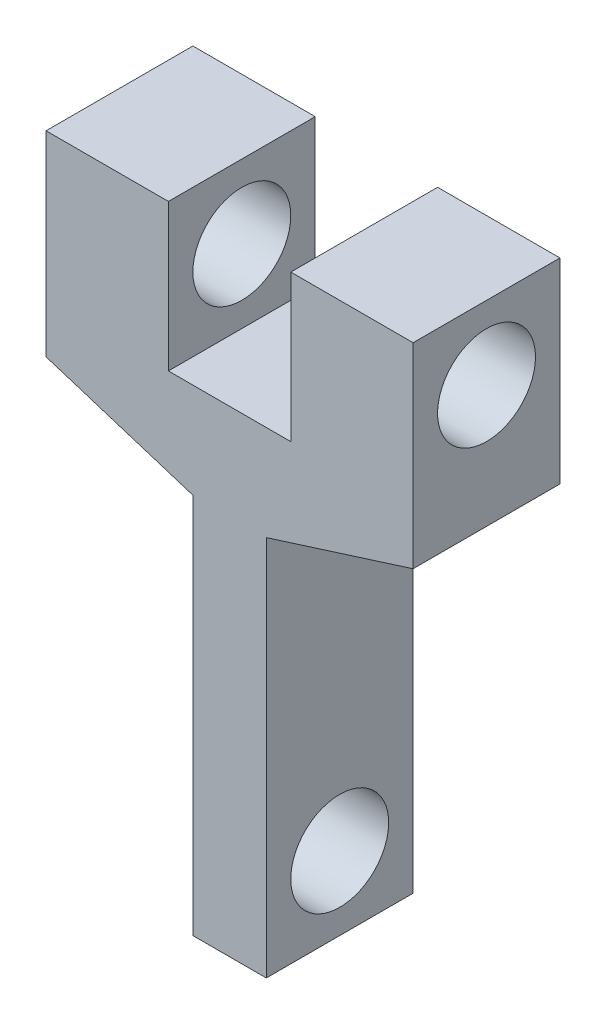
SolidWorks part; units mm, degrees
ref_plane "Plan de face" through (0, 0, 0) normal (0, 0, 1) x (1, 0, 0)
ref_plane "Plan de dessus" through (0, 0, 0) normal (0, 1, 0) x (1, 0, 0)
ref_plane "Plan de droite" through (0, 0, 0) normal (1, 0, 0) x (0, 0, -1)
sketch "Esquisse1" plane through (0, 0, 0) normal (0, 0, 1) x (1, 0, 0)
  line L0 (-7.5, 7.7412) -> (-1.5, 5.8447)
  line L1 (-1.5, -9.7412) -> (1.5, -9.7412)
  line L2 (0, 0) -> (0, 9.7412) construction
  line L3 (-2.5, 9.7412) -> (2.5, 9.7412)
  line L4 (1.5, 5.8447) -> (1.5, -9.7412)
  line L5 (-2.5, -9.7412) -> (2.5, 9.7412) construction
  line L6 (-2.5, 9.7412) -> (2.5, -9.7412) construction
  line L8 (-2.5, 9.7412) -> (-2.5, 15.7412)
  line L9 (-2.5, 15.7412) -> (-7.5, 15.7412)
  line L10 (-7.5, 7.7412) -> (-7.5, 15.7412)
  line L11 (-1.5, 5.8447) -> (-1.5, -9.7412)
  line L12 (7.5, 7.7412) -> (7.5, 15.7412)
  line L13 (2.5, 15.7412) -> (7.5, 15.7412)
  line L14 (2.5, 9.7412) -> (2.5, 15.7412)
  line L16 (7.5, 7.7412) -> (1.5, 5.8447)
  point P0 (0, 0)
  dimension "D1" = 5
  dimension "D2" = 8
  dimension "D3" = 5
  dimension "D4" = 6
  dimension "D5" = 1.5
extrude "Boss.-Extru.1" add sketch "Esquisse1" along normal blind 6
sketch "Esquisse2" plane through (7.5, 0, 0) normal (1, 0, 0) x (0, 0, -1)
  line L0 (-6, 15.7412) -> (0, 9.7412) construction
  line L1 (0, 9.7412) -> (-3, 9.7412) construction
  line L2 (-6, 9.7412) -> (0, 9.7412) construction
  line L3 (-3, 9.7412) -> (-3, 15.7412) construction
  line L4 (-6, 15.7412) -> (0, 15.7412) construction
  circle A0 centre (-3, 12.7412) radius 2
  dimension "D1" = 4
extrude "Enlèv. mat.-Extru.1" cut sketch "Esquisse2" against normal up to surface (15 mm away) up to face at (-7.5, 11.7412, 3)
sketch "Esquisse3" plane through (1.5, 0, 0) normal (1, 0, 0) x (0, 0, -1)
  line L0 (-6, -9.7412) -> (0, -3.7412) construction
  line L1 (0, -9.7412) -> (0, 5.8447) construction
  line L2 (0, -3.7412) -> (-6, -3.7412) construction
  line L3 (-6, -9.7412) -> (-6, 5.8447) construction
  line L4 (-6, -3.7412) -> (0, -9.7412) construction
  line L5 (-6, -9.7412) -> (0, -9.7412) construction
  circle A0 centre (-3, -6.7412) radius 2
  dimension "D1" = 4
  dimension "D2" = 3
extrude "Enlèv. mat.-Extru.2" cut sketch "Esquisse3" against normal up to surface (3 mm away) up to face at (-1.5, -1.9482, 3)
